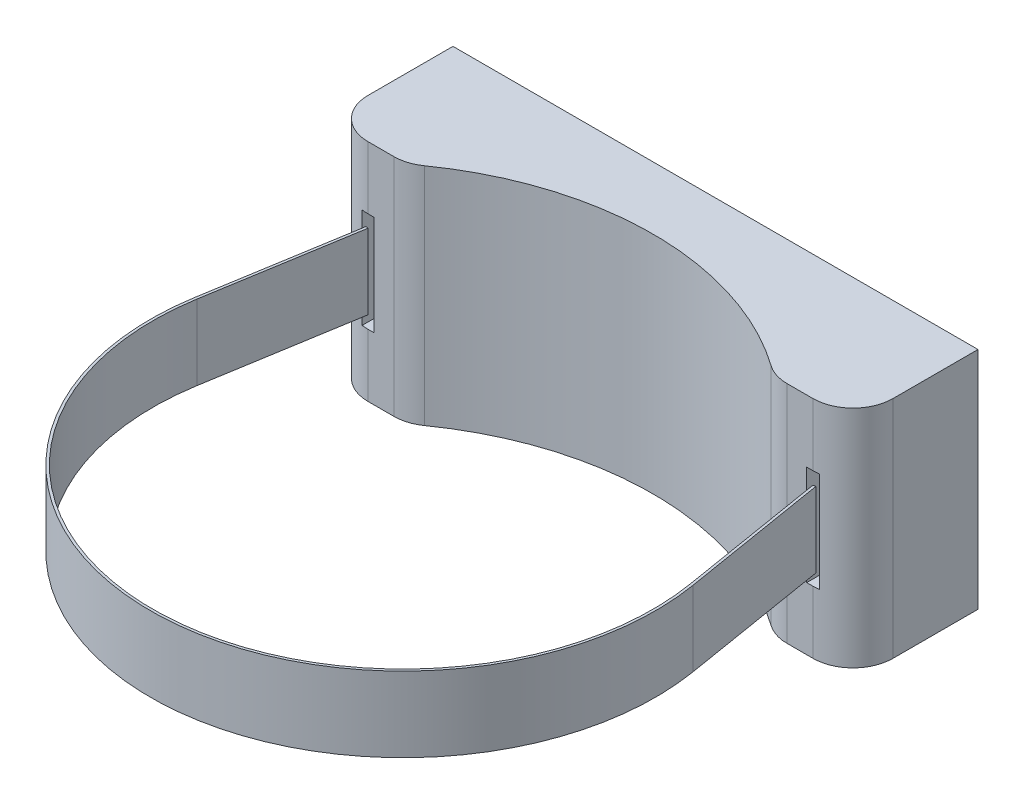
SolidWorks part; units mm, degrees
material "PPE"
ref_plane "Front" through (0, 0, 0) normal (0, 0, 1) x (1, 0, 0)
ref_plane "Top" through (0, 0, 0) normal (0, 1, 0) x (1, 0, 0)
ref_plane "Right" through (0, 0, 0) normal (1, 0, 0) x (0, 0, -1)
sketch "Sketch1" plane through (0, 0, 0) normal (0, 1, 0) x (1, 0, 0)
  line L0 (0, 0) -> (0, -152.4) construction
  line L1 (-133.35, 31.75) -> (133.35, 31.75)
  line L2 (-133.35, 31.75) -> (-133.35, -31.75)
  line L3 (-133.35, -31.75) -> (-93.1093, -31.75)
  line L4 (133.35, 31.75) -> (133.35, -31.75)
  line L5 (-133.35, 31.75) -> (133.35, -31.75) construction
  line L6 (-133.35, -31.75) -> (133.35, 31.75) construction
  line L7 (93.1093, -31.75) -> (133.35, -31.75)
  arc A0 (93.1093, -31.75) -> (-93.1093, -31.75) centre (0, -152.4) ccw
  point P0 (0, 0)
  dimension "D3" = 304.8
  dimension "D1" = 266.7
  dimension "D2" = 63.5
  dimension "D4" = 152.4
extrude "Boss-Extrude1" add sketch "Sketch1" along normal blind 114.3
fillet "Fillet1" radius 20.32 2 edges at (133.35, 57.15, 31.75) (-133.35, 57.15, 31.75)
fillet "Fillet2" radius 20.32 2 edges at (93.1093, 57.15, 31.75) (-93.1093, 57.15, 31.75)
sketch "Sketch2" plane through (0, 0, 31.75) normal (0, 0, 1) x (1, 0, 0)
  line L0 (-113.03, 114.3) -> (-113.03, 0) construction
  line L1 (-116.205, 82.55) -> (-109.855, 82.55)
  line L2 (-116.205, 82.55) -> (-116.205, 31.75)
  line L3 (-116.205, 31.75) -> (-109.855, 31.75)
  line L4 (-109.855, 82.55) -> (-109.855, 31.75)
  line L5 (-116.205, 82.55) -> (-109.855, 31.75) construction
  line L6 (-116.205, 31.75) -> (-109.855, 82.55) construction
  line L7 (113.03, 0) -> (113.03, 114.3) construction
  line L8 (109.855, 82.55) -> (116.205, 82.55)
  line L9 (109.855, 82.55) -> (109.855, 31.75)
  line L10 (109.855, 31.75) -> (116.205, 31.75)
  line L11 (116.205, 82.55) -> (116.205, 31.75)
  line L12 (109.855, 82.55) -> (116.205, 31.75) construction
  line L13 (109.855, 31.75) -> (116.205, 82.55) construction
  point P0 (-113.03, 57.15)
  point P7 (113.03, 57.15)
  dimension "D1" = 50.8
  dimension "D2" = 6.35
extrude "Cut-Extrude1" cut sketch "Sketch2" against normal through all
sketch "Sketch3" plane through (0, 31.75, 0) normal (0, 1, 0) x (1, 0, 0)
  line L0 (0, 0) -> (0, -127) construction
  line L1 (-113.03, -31.75) -> (-125.3136, -106.3721)
  line L2 (113.03, -31.75) -> (125.3136, -106.3721)
  arc A0 (-125.3136, -106.3721) -> (125.3136, -106.3721) centre (0, -127) ccw
  dimension "D1" = 254
  dimension "D2" = 127
extrude "Extrude-Thin1" add sketch "Sketch3" along normal blind 38.1 from offset 6.35 separate body thin thin type one direction wall 1.27
